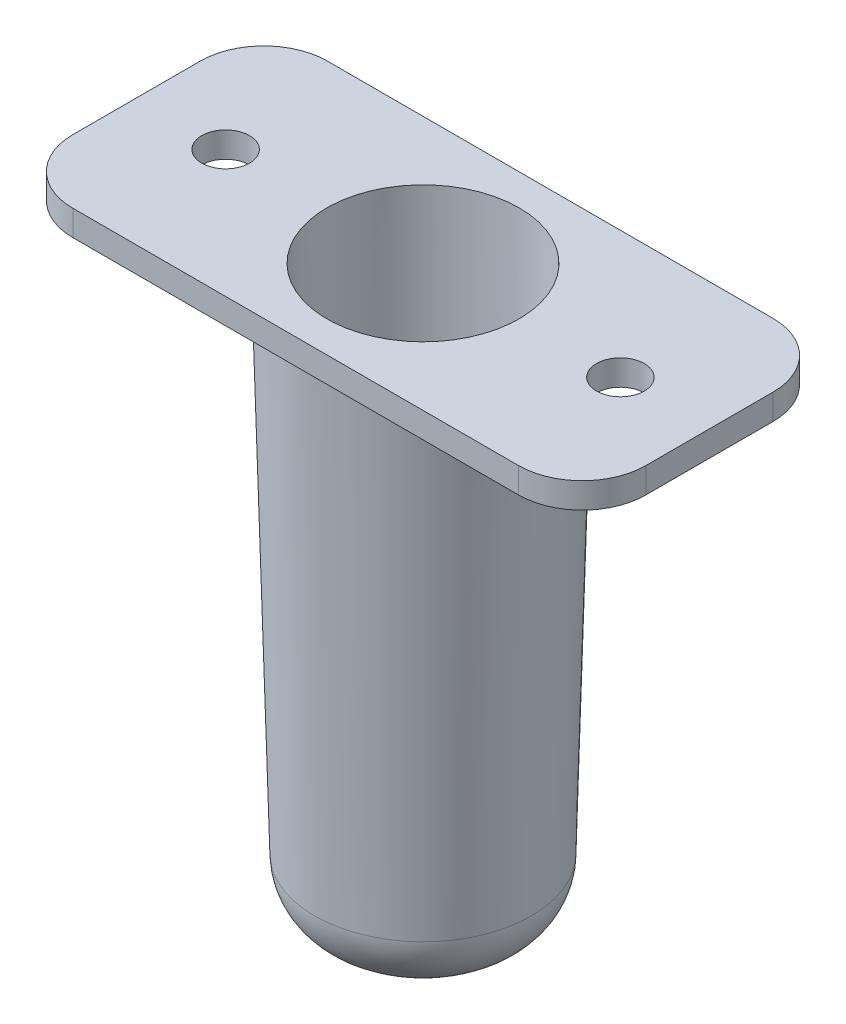
SolidWorks part; units mm, degrees
material "ABS"
ref_plane "Front Plane" through (0, 0, 0) normal (0, 0, 1) x (1, 0, 0)
ref_plane "Top Plane" through (0, 0, 0) normal (0, 1, 0) x (1, 0, 0)
ref_plane "Right Plane" through (0, 0, 0) normal (1, 0, 0) x (0, 0, -1)
sketch "Sketch1" plane through (0, 0, 0) normal (0, 1, 0) x (1, 0, 0)
  line L1 (-22.225, -12.7) -> (22.225, -12.7)
  line L2 (-28.575, -6.35) -> (-28.575, 6.35)
  line L3 (-22.225, 12.7) -> (22.225, 12.7)
  line L4 (28.575, -6.35) -> (28.575, 6.35)
  line L5 (-28.575, -12.7) -> (28.575, 12.7) construction
  line L6 (-28.575, 12.7) -> (28.575, -12.7) construction
  arc A0 (28.575, -6.35) -> (22.225, -12.7) centre (22.225, -6.35) cw
  arc A1 (22.225, 12.7) -> (28.575, 6.35) centre (22.225, 6.35) cw
  arc A2 (-22.225, 12.7) -> (-28.575, 6.35) centre (-22.225, 6.35) ccw
  arc A3 (-28.575, -6.35) -> (-22.225, -12.7) centre (-22.225, -6.35) ccw
  point P0 (0, 0)
  dimension "D3" = 6.35
  dimension "D1" = 57.15
  dimension "D2" = 25.4
extrude "Boss-Extrude1" add sketch "Sketch1" along normal blind 2.54
sketch "Sketch2" plane through (0, 0, 0) normal (0, -1, 0) x (1, 0, 0)
  circle A0 centre (0, 0) radius 12.065
  dimension "D1" = 24.13
extrude "Boss-Extrude2" add sketch "Sketch2" along normal blind 54.61
draft "Draft2" type of draft neutral plane draft angle 1.5 faces to draft 1 face at (0, -54.61, -12.065) neutral plane through (22.225, 0, 6.35) neutral plane normal (0, -1, 0) parameters "D1"=1.5
fillet "Fillet2" radius 6.35 1 edges at (0, -54.61, -10.635)
shell "Shell1" thickness 2.54 removed face at (0, 2.54, 0)
sketch "Sketch3" plane through (0, 0, 0) normal (0, -1, 0) x (1, 0, 0)
  line L0 (0, 0) -> (0, 20.4983) construction
  line L1 (28.575, 6.35) -> (28.575, -6.35) construction
  circle A0 centre (19.685, 0) radius 2.3813
  dimension "D2" = 4.7625
  dimension "D1" = 8.89
extrude "Cut-Extrude1" cut sketch "Sketch3" against normal up to next
mirror "Mirror1" about plane through (0, 0, 0) normal (1, 0, 0) of "Cut-Extrude1"
